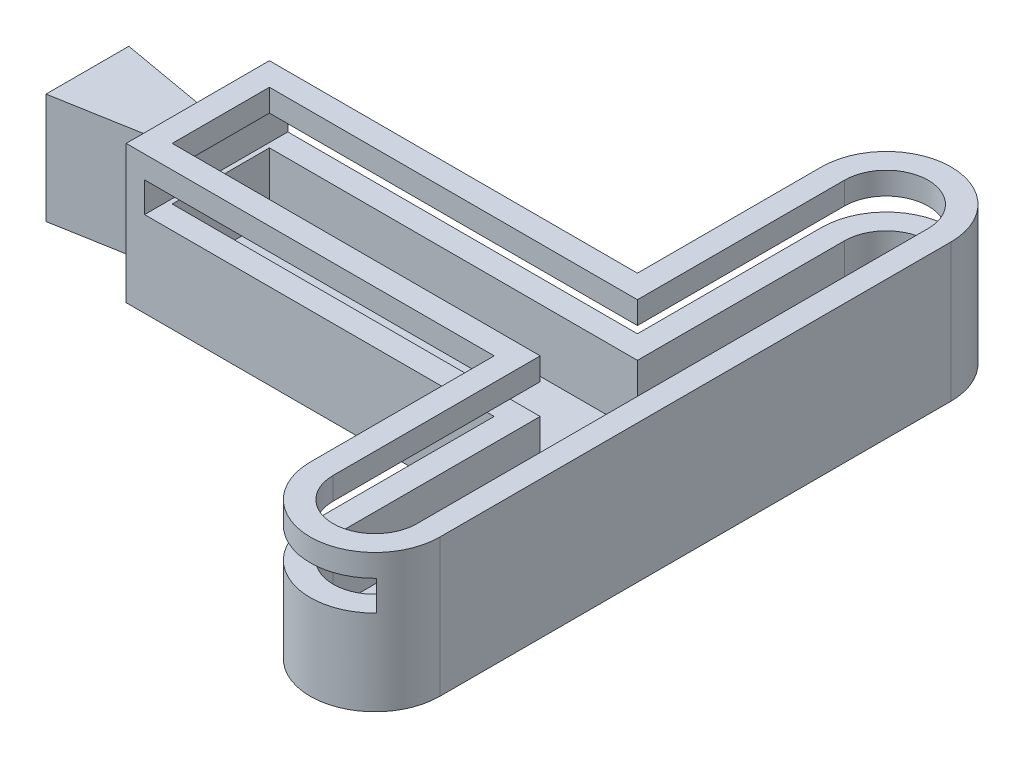
SolidWorks part; units mm, degrees
ref_plane "Front Plane" through (0, 0, 0) normal (0, 0, 1) x (1, 0, 0)
ref_plane "Top Plane" through (0, 0, 0) normal (0, 1, 0) x (1, 0, 0)
ref_plane "Right Plane" through (0, 0, 0) normal (1, 0, 0) x (0, 0, -1)
sketch "Sketch1" plane through (0, 0, 0) normal (0, 1, 0) x (1, 0, 0)
  line L0 (0, 11.43) -> (0, -11.43)
  line L1 (0, 11.43) -> (30.48, 6.0556)
  line L2 (0, -11.43) -> (30.48, -6.0556)
  line L3 (30.48, 6.0556) -> (30.48, 19.7716)
  line L4 (30.48, -6.0556) -> (30.48, -19.7716)
  line L5 (30.48, 6.0556) -> (30.48, -6.0556) construction
  line L6 (0, 0) -> (30.48, 0) construction
  line L7 (30.48, 19.7716) -> (132.08, 19.7716)
  line L8 (30.48, -19.7716) -> (132.08, -19.7716)
  line L9 (132.08, 19.7716) -> (132.08, 70.5716)
  line L10 (132.08, -19.7716) -> (132.08, -70.5716)
  line L12 (167.894, 70.5716) -> (167.894, -70.5716)
  arc A0 (167.894, 70.5716) -> (132.08, 70.5716) centre (149.987, 70.5716) ccw
  arc A1 (167.894, -70.5716) -> (132.08, -70.5716) centre (149.987, -70.5716) cw
  point P3 (0, 0)
  dimension "D1" = 22.86
  dimension "D2" = 30.48
  dimension "D3" = 80
  dimension "D4" = 80
  dimension "D5" = 39.5431
  dimension "D6" = 13.716
  dimension "D7" = 101.6
  dimension "D8" = 101.6
  dimension "D9" = 13.716
  dimension "D10" = 50.8
  dimension "D11" = 35.814
extrude "Boss-Extrude1" add sketch "Sketch1" along normal blind 38.1
sketch "Sketch5" plane through (0, 38.1, 0) normal (0, 1, 0) x (1, 0, 0)
  line L0 (0, -11.43) -> (0, 11.43)
  line L1 (0, -11.43) -> (30.48, -6.0556) construction
  line L2 (0, 11.43) -> (0, -11.43) construction
  line L3 (0, 11.43) -> (0.2056, 11.5763)
  line L4 (30.48, 6.0556) -> (30.48, -6.0556)
  line L5 (30.48, -6.0556) -> (0, -11.43)
  line L6 (0.2056, 11.5763) -> (30.48, 6.0556)
  dimension "D1" = 79.665
extrude "Cut-Extrude10" cut sketch "Sketch5" against normal blind 7.62
shell "Shell2" thickness 6.35 removed face at (115.6335, 38.1, 0)
sketch "Sketch6" plane through (0, 0, 19.7716) normal (0, 0, 1) x (1, 0, 0)
  line L8 (35.56, 31.9176) -> (35.56, 23.6094)
  line L9 (35.56, 23.6094) -> (162.814, 23.6094)
  line L10 (162.814, 23.6094) -> (162.814, 31.9176)
  line L11 (162.814, 31.9176) -> (35.56, 31.9176)
  line L12 (30.48, 38.1) -> (30.48, 0) construction
  line L13 (167.894, 38.1) -> (167.894, 0) construction
  line L14 (30.48, 38.1) -> (132.08, 38.1) construction
  line L15 (30.48, 0) -> (132.08, 0) construction
  dimension "D1" = 5.08
  dimension "D2" = 5.08
  dimension "D3" = 127.254
  dimension "D4" = 6.1824
  dimension "D5" = 23.6094
extrude "Cut-Extrude11" cut sketch "Sketch6" against normal through all both and the other way through all
